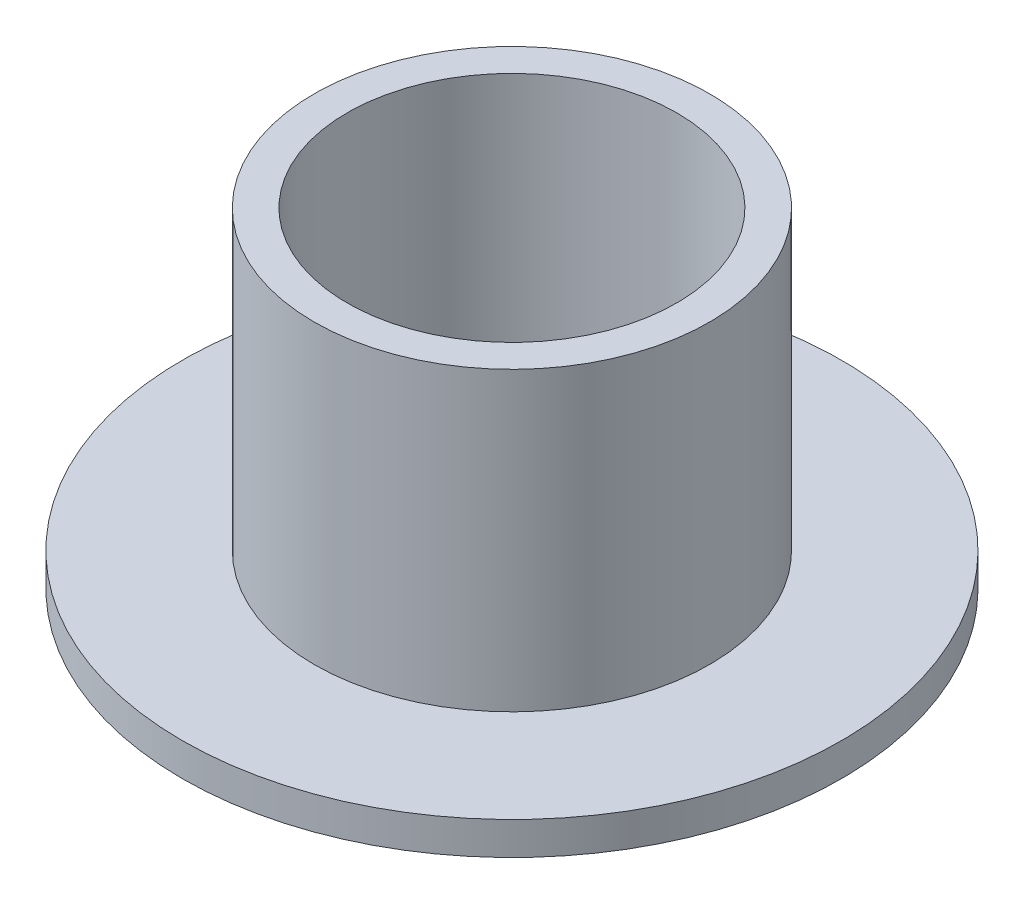
SolidWorks part; units mm, degrees
ref_plane "前视基准面" through (0, 0, 0) normal (0, 0, 1) x (1, 0, 0)
ref_plane "上视基准面" through (0, 0, 0) normal (0, 1, 0) x (1, 0, 0)
ref_plane "右视基准面" through (0, 0, 0) normal (1, 0, 0) x (0, 0, -1)
other "Configuration Table"
sketch "草图1" plane through (0, 0, 0) normal (0, 1, 0) x (1, 0, 0)
  circle A0 centre (0, 0) radius 5
  dimension "D1" = 10
extrude "凸台-拉伸1" add sketch "草图1" along normal blind 0.5
sketch "草图2" plane through (0, 0.5, 0) normal (0, 1, 0) x (1, 0, 0)
  circle A0 centre (0, 0) radius 3
  dimension "D1" = 6
extrude "凸台-拉伸2" add sketch "草图2" along normal blind 4.5
sketch "草图3" plane through (0, 0, 0) normal (0, -1, 0) x (1, 0, 0)
  circle A0 centre (0, 0) radius 2.5
  dimension "D1" = 5
extrude "切除-拉伸1" cut sketch "草图3" against normal through all
ref_axis "基准轴1" through (0, 10.1247, 0) along (0, -1, 0)
